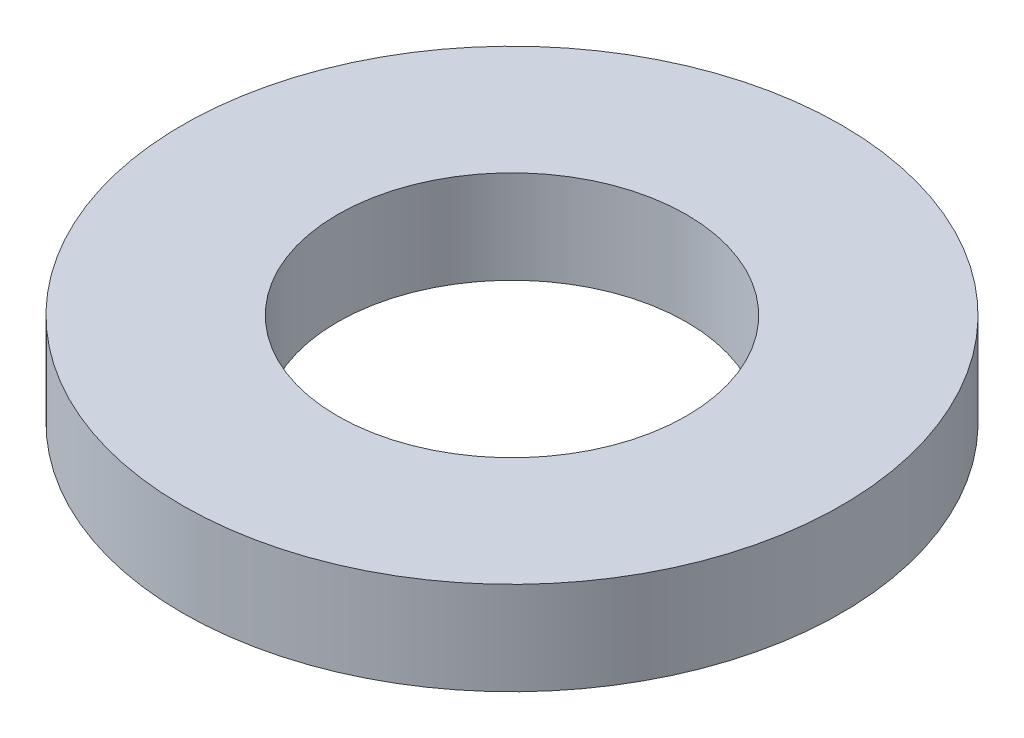
SolidWorks part; units mm, degrees
ref_plane "Front Plane" through (0, 0, 0) normal (0, 0, 1) x (1, 0, 0)
ref_plane "Top Plane" through (0, 0, 0) normal (0, 1, 0) x (1, 0, 0)
ref_plane "Right Plane" through (0, 0, 0) normal (1, 0, 0) x (0, 0, -1)
sketch "Sketch1" plane through (0, 0, 0) normal (0, 1, 0) x (1, 0, 0)
  circle A0 centre (0, 0) radius 85
  dimension "FLANGE_OD" = 170
extrude "Boss-Extrude1" add sketch "Sketch1" along normal blind 24
sketch "Sketch2" plane through (0, 0, 0) normal (0, 1, 0) x (1, 0, 0)
  circle A0 centre (0, 0) radius 45
  dimension "BORE_D" = 90
extrude "Cut-Extrude1" cut sketch "Sketch2" along normal through all
sketch "Sketch3" plane through (0, 24, 0) normal (0, 1, 0) x (1, 0, 0)
  circle A0 centre (0, 0) radius 33.0435 construction
  circle A1 centre (-33.0435, 0) radius 2.5781
  dimension "BOLT_D" = 5.1562
  dimension "BOLT_PCD" = 66.0871
extrude "Cut-Extrude2" cut sketch "Sketch3" against normal blind 19.6896 rebuild error yes
pattern_circular "CirPattern1" count 6 over 360 rebuild error yes
